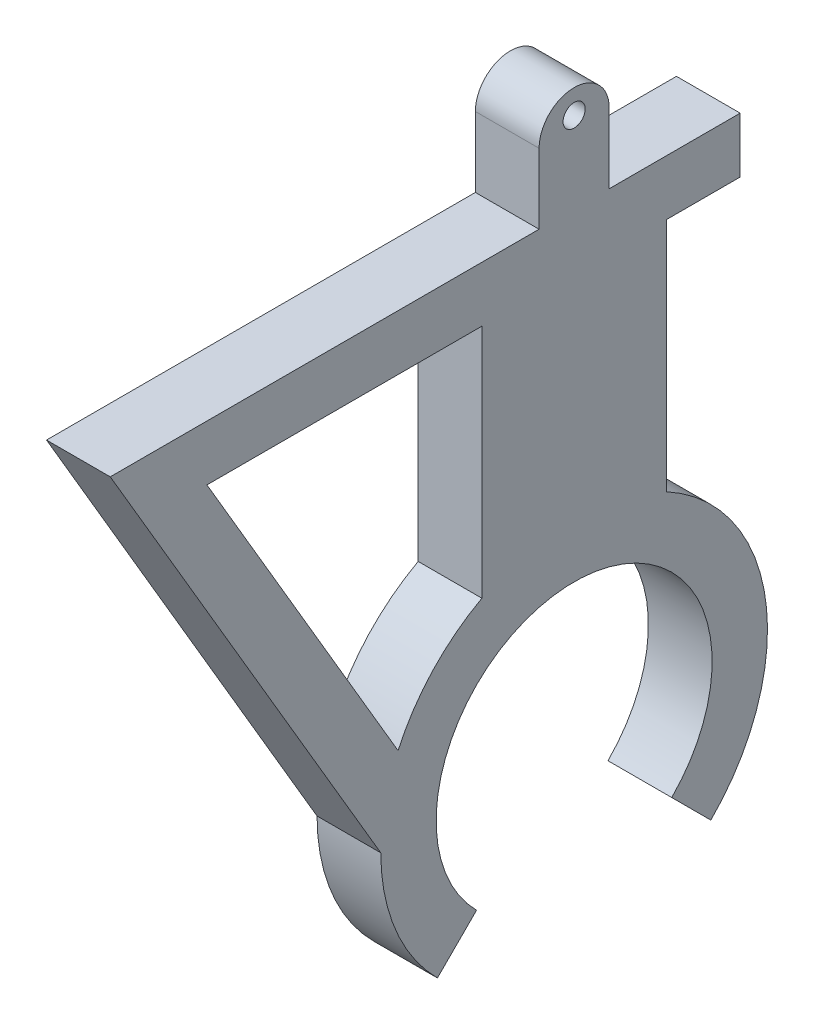
SolidWorks part; units mm, degrees
ref_plane "Front Plane" through (0, 0, 0) normal (0, 0, 1) x (1, 0, 0)
ref_plane "Top Plane" through (0, 0, 0) normal (0, 1, 0) x (1, 0, 0)
ref_plane "Right Plane" through (0, 0, 0) normal (1, 0, 0) x (0, 0, -1)
sketch "Sketch1" plane through (0, 0, 0) normal (1, 0, 0) x (0, 0, -1)
  line L0 (-2.6446, -2.6446) -> (2.6446, -2.6446) construction
  line L1 (-2.6446, -2.6446) -> (-3.7052, -3.7052)
  line L2 (3.7052, -3.7052) -> (2.6446, -2.6446)
  line L3 (0, 0) -> (0, 6.3411) construction
  line L4 (-2.5, 12.4907) -> (-0.95, 12.4907)
  line L5 (-2.5, 12.4907) -> (-2.5, 4.6052)
  line L6 (-0.95, 14.3907) -> (-0.95, 12.4907)
  line L7 (2.5, 12.4907) -> (2.5, 4.6052)
  line L8 (-2.5, 12.4907) -> (2.5, 4.6052) construction
  line L9 (-2.5, 4.6052) -> (2.5, 12.4907) construction
  line L10 (-0.95, 14.3907) -> (0.95, 14.3907) construction
  line L11 (0.95, 12.4907) -> (2.5, 12.4907)
  line L12 (0.95, 14.3907) -> (0.95, 12.4907)
  line L13 (-0.95, 14.3907) -> (0.95, 12.4907) construction
  line L14 (-0.95, 12.4907) -> (0.95, 14.3907) construction
  line L15 (-2.5, 12.4907) -> (-12.5716, 12.4907)
  line L16 (-12.5716, 12.4907) -> (-5.24, 0)
  line L17 (-2.5, 10.9907) -> (-9.9519, 10.9907)
  line L18 (-9.9519, 10.9907) -> (-4.7717, 2.1653)
  line L19 (-9.9519, 10.9907) -> (-3.9464, 0.7593) construction
  line L20 (-57.8952, 12.4907) -> (-62.7212, 12.4907) construction
  line L21 (2.5, 12.4907) -> (4.5, 12.4907)
  line L22 (2.5, 12.4907) -> (2.5, 10.9907)
  line L23 (2.5, 10.9907) -> (4.5, 10.9907)
  line L24 (4.5, 12.4907) -> (4.5, 10.9907)
  arc A0 (-2.6446, -2.6446) -> (2.6446, -2.6446) centre (0, 0) cw
  arc A1 (-3.7052, -3.7052) -> (-2.5, 4.6052) centre (0, 0) cw
  arc A2 (2.5, 4.6052) -> (3.7052, -3.7052) centre (0, 0) cw
  arc A3 (-3.7052, -3.7052) -> (3.7052, -3.7052) centre (0, 0) cw construction
  arc A4 (-0.95, 14.3907) -> (0.95, 14.3907) centre (0, 14.3907) cw
  circle A5 centre (0, 14.6907) radius 0.3
  point P7 (0, 8.5479)
  point P12 (0, 3.74)
  point P16 (0, 14.3907)
  point P17 (0, 13.4407)
  dimension "D1" = 3.74
  dimension "D3" = 1.5
  dimension "D6" = 1.9
  dimension "D8" = 0.6
  dimension "D9" = 1.5
  dimension "D2" = 90
  dimension "D5" = 5
  dimension "D7" = 1.9
  dimension "D10" = 2
extrude "Boss-Extrude1" add sketch "Sketch1" along normal blind 1.7272 contours A4 L6 L4 L5 A1 L1 A0 L2 A2 L7 L11 L12 A5 | L16 A1 L18 L17 L5 L15 | L24 L21 L7 L23 region at (0, 5.8984, 0) region at (0, 6.3266, 8.7674) region at (0, 11.7407, -3.5)
